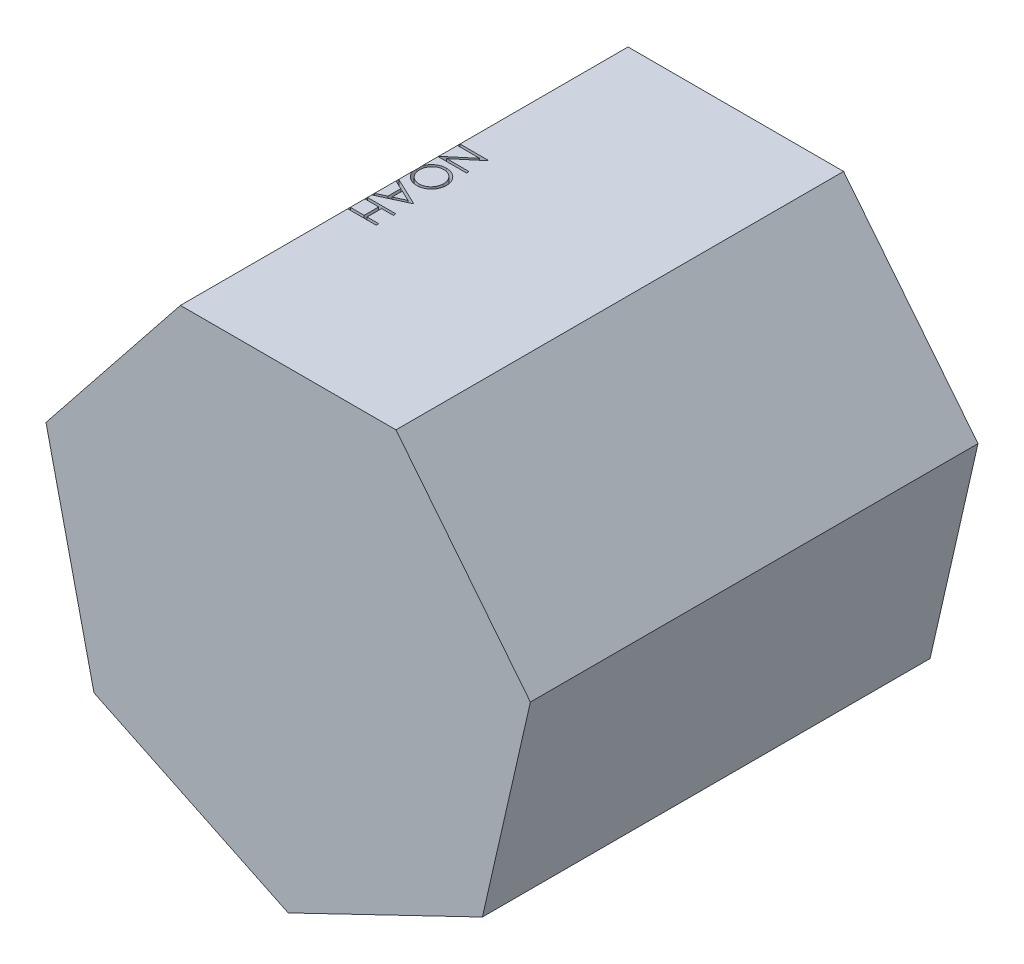
SolidWorks part; units mm, degrees
ref_plane "Front Plane" through (0, 0, 0) normal (0, 0, 1) x (1, 0, 0)
ref_plane "Top Plane" through (0, 0, 0) normal (0, 1, 0) x (1, 0, 0)
ref_plane "Right Plane" through (0, 0, 0) normal (1, 0, 0) x (0, 0, -1)
sketch "Sketch1" plane through (0, 0, 0) normal (0, 0, 1) x (1, 0, 0)
  line L1 (0, -110.9916) -> (86.7767, -69.2021)
  line L2 (86.7767, -69.2021) -> (108.2088, 24.698)
  line L3 (108.2088, 24.698) -> (48.1575, 100)
  line L4 (48.1575, 100) -> (-48.1575, 100)
  line L5 (-48.1575, 100) -> (-108.2088, 24.698)
  line L6 (-108.2088, 24.698) -> (-86.7767, -69.2021)
  line L7 (-86.7767, -69.2021) -> (0, -110.9916)
  circle A0 centre (0, 0) radius 100 construction
  dimension "D1" = 200
extrude "Boss-Extrude1" add sketch "Sketch1" along normal blind 200
sketch "Sketch2" plane through (-78.1831, 62.349, 0) normal (-0.7818, 0.6235, 0) x (0, 0, 1)
  text T0 "Andres" font "Century Gothic" height 20
extrude "Cut-Extrude1" cut sketch "Sketch2" against normal blind 1
sketch "Sketch4" plane through (-97.4928, -22.2521, 0) normal (-0.9749, -0.2225, 0) x (0, 0, 1)
  text T0 "Billy" font "Century Gothic" height 20
extrude "Cut-Extrude3" cut sketch "Sketch4" against normal blind 1
sketch "Sketch7" plane through (-43.3884, -90.0969, 0) normal (-0.4339, -0.901, 0) x (-0.901, 0.4339, 0)
  text T0 "ALEX" font "Century Gothic" height in points 72
extrude "Cut-Extrude5" cut sketch "Sketch7" against normal blind 2
sketch "Sketch8" plane through (0, 100, 0) normal (0, 1, 0) x (1, 0, 0)
  text T0 "NOAH" font "Century Gothic" height in points 48
extrude "Cut-Extrude6" cut sketch "Sketch8" against normal blind 10
sketch "Sketch9" plane through (43.3884, -90.0969, 0) normal (0.4339, -0.901, 0) x (-0.901, -0.4339, 0)
  text T0 "ANIKA" font "Century Gothic" height 12.5
extrude "Cut-Extrude7" cut sketch "Sketch9" against normal blind 5
